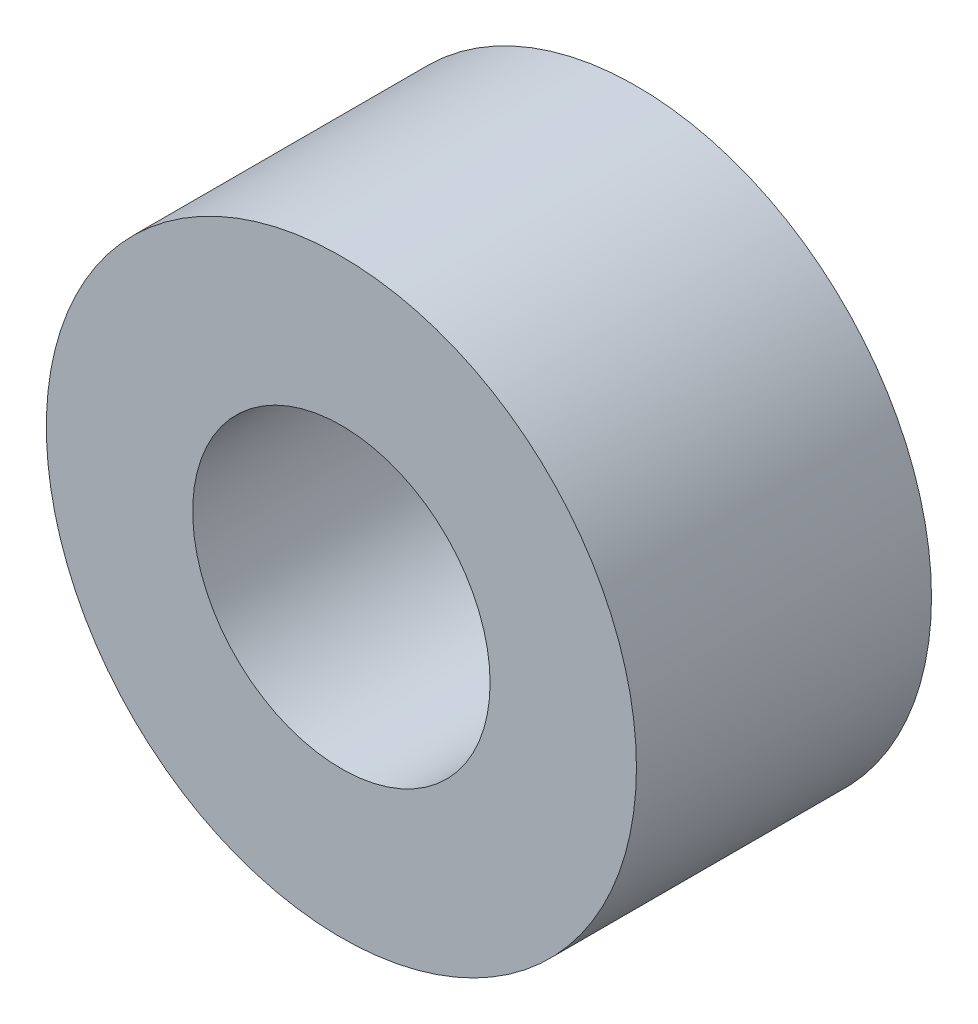
SolidWorks part; units mm, degrees
ref_plane "Front Plane" through (0, 0, 0) normal (0, 0, 1) x (1, 0, 0)
ref_plane "Top Plane" through (0, 0, 0) normal (0, 1, 0) x (1, 0, 0)
ref_plane "Right Plane" through (0, 0, 0) normal (1, 0, 0) x (0, 0, -1)
sketch "Sketch1" plane through (0, 0, 0) normal (0, 0, 1) x (1, 0, 0)
  circle A0 centre (0, 0) radius 6.35
  circle A1 centre (0, 0) radius 3.2004
  dimension "OD" = 12.7
  dimension "ID" = 6.4008
extrude "Extrude1" add sketch "Sketch1" along normal mid plane 6.35
sketch "Sketch2" plane through (0, 0, 0) normal (1, 0, 0) x (0, 0, -1)
  line L0 (-3.175, -3.2004) -> (3.175, -3.2004) construction
  line L3 (3.175, 3.2004) -> (-3.175, 3.2004) construction
  line L5 (-3.175, -3.2004) -> (3.175, -3.2004)
  line L6 (3.175, 3.2004) -> (-3.175, 3.2004)
sketch "Sketch4" plane through (0, 0, 3.175) normal (0, 0, 1) x (1, 0, 0)
  line L0 (0, 0) -> (-2.263, 2.263)
  line L1 (0, -5.2388) -> (0, 5.2388) construction
  circle A0 centre (0, 0) radius 3.2004 construction
  dimension "D1" = 45
